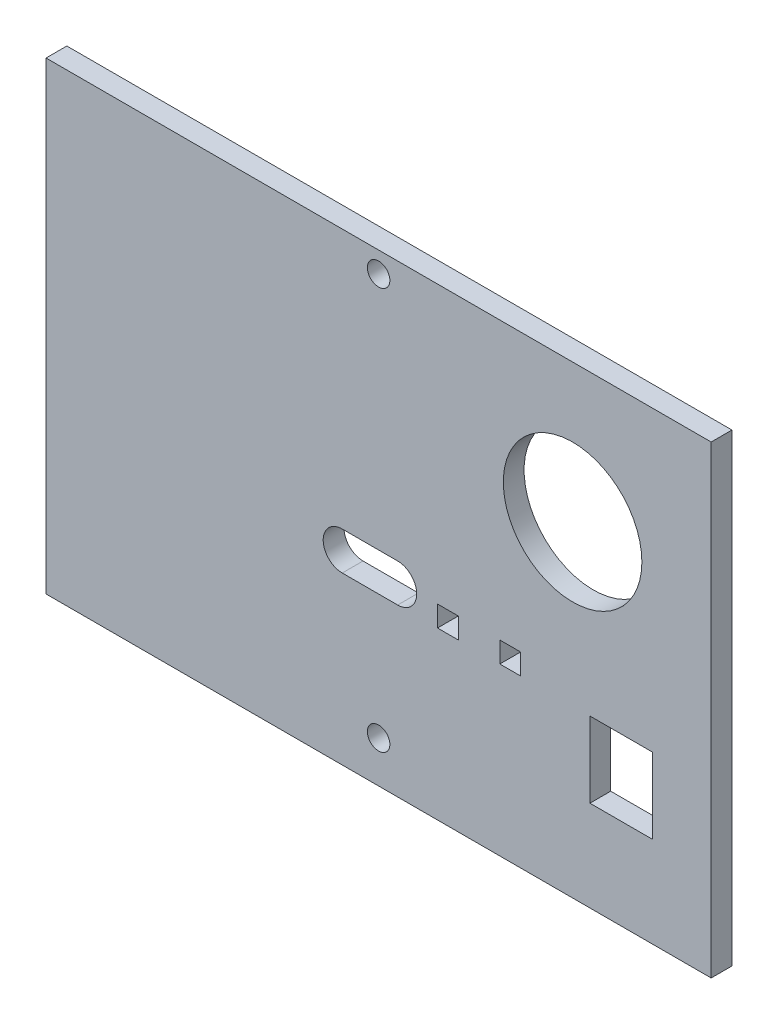
SolidWorks part; units mm, degrees
ref_plane "Alzado" through (0, 0, 0) normal (0, 0, 1) x (1, 0, 0)
ref_plane "Planta" through (0, 0, 0) normal (0, 1, 0) x (1, 0, 0)
ref_plane "Vista lateral" through (0, 0, 0) normal (1, 0, 0) x (0, 0, -1)
sketch "Croquis6" plane through (0, 0, 0) normal (0, 0, 1) x (1, 0, 0)
  line L1 (-48, -33.5) -> (48, -33.5)
  line L2 (-48, -33.5) -> (-48, 33.5)
  line L3 (-48, 33.5) -> (48, 33.5)
  line L4 (48, -33.5) -> (48, 33.5)
  line L5 (-48, -33.5) -> (48, 33.5) construction
  line L6 (-48, 33.5) -> (48, -33.5) construction
  point P0 (0, 0)
  dimension "D1" = 96
  dimension "D2" = 67
extrude "Saliente-Extruir1" add sketch "Croquis6" along normal blind 3
sketch "Croquis7" plane through (0, 0, 0) normal (0, 0, 1) x (1, 0, 0)
  line L5 (48, 33.5) -> (-48, 33.5) construction
  line L13 (-48, -33.5) -> (48, -33.5) construction
  line L14 (30.5, -9.5) -> (39.5, -9.5)
  line L15 (30.5, -9.5) -> (30.5, -20.4)
  line L16 (30.5, -20.4) -> (39.5, -20.4)
  line L17 (39.5, -9.5) -> (39.5, -20.4)
  line L18 (30.5, -9.5) -> (39.5, -20.4) construction
  line L19 (30.5, -20.4) -> (39.5, -9.5) construction
  line L20 (-48, 33.5) -> (-48, -33.5) construction
  line L21 (2.75, -6.75) -> (-5.25, -6.75) construction
  line L22 (2.75, -9.5) -> (-5.25, -9.5)
  line L23 (2.75, -4) -> (-5.25, -4)
  line L24 (48, -33.5) -> (48, 33.5) construction
  line L25 (8.5, -9.5) -> (11.5, -9.5)
  line L26 (8.5, -9.5) -> (8.5, -6.5)
  line L27 (8.5, -6.5) -> (11.5, -6.5)
  line L28 (11.5, -9.5) -> (11.5, -6.5)
  line L29 (8.5, -9.5) -> (11.5, -6.5) construction
  line L30 (8.5, -6.5) -> (11.5, -9.5) construction
  line L32 (17.5, -9.5) -> (20.5, -9.5)
  line L33 (17.5, -9.5) -> (17.5, -6.5)
  line L34 (17.5, -6.5) -> (20.5, -6.5)
  line L35 (20.5, -9.5) -> (20.5, -6.5)
  line L36 (17.5, -9.5) -> (20.5, -6.5) construction
  line L37 (17.5, -6.5) -> (20.5, -9.5) construction
  arc A0 (2.75, -9.5) -> (2.75, -4) centre (2.75, -6.75) ccw
  arc A1 (-5.25, -4) -> (-5.25, -9.5) centre (-5.25, -6.75) ccw
  circle A2 centre (0, -27.5) radius 1.625 construction
  circle A3 centre (0, 30.5) radius 1.625 construction
  circle A4 centre (0, -27.5) radius 1.625
  circle A5 centre (0, 30.5) radius 1.625
  circle A6 centre (28, 13.5) radius 10
  point P2 (0, 0)
  point P3 (35, 21.3965)
  point P4 (35, 19.4387)
  point P5 (19, 15.7094)
  point P12 (35, -14.95)
  point P23 (-1.25, -6.75)
  point P34 (10, -8)
  point P41 (19, -8)
  dimension "D11" = 42.75
  dimension "D12" = 39.5
  dimension "D2" = 20
  dimension "D3" = 20
  dimension "D4" = 20
  dimension "D5" = 10.9
  dimension "D6" = 9
  dimension "D7" = 24
  dimension "D8" = 87.5
  dimension "D9" = 8
  dimension "D10" = 5.5
  dimension ".5" = 29.5
  dimension "D13" = 24
  dimension "D14" = 3
  dimension "D15" = 6
extrude "Cortar-Extruir1" cut sketch "Croquis7" along normal through all
sketch "Sketch3" plane through (0, 0, 0) normal (0, 0, -1) x (-1, 0, 0)
  line L0 (0.3471, -0.1213) -> (0.4863, 0.0193)
  line L1 (0.4863, 0.0193) -> (-0.8214, 1.3302)
  line L2 (-2.1938, 4.0023) -> (-2.1938, 5.2355)
  line L3 (-2.1938, 5.2355) -> (-2.305, 5.3057)
  line L4 (-1.1344, 5.3242) -> (-1.2539, 5.2509)
  line L5 (-1.2539, 5.2509) -> (-1.2538, 4.1659)
  line L6 (-1.2538, 4.1659) -> (-1.2537, 3.0809)
  line L7 (-1.2537, 3.0809) -> (-0.2805, 2.0692)
  line L8 (0.7386, 5.1898) -> (0.7386, 9.3416)
  line L9 (0.7386, 9.3416) -> (0.366, 9.6084)
  line L10 (2.1031, 9.6083) -> (1.6769, 9.3415)
  line L11 (1.6769, 9.3415) -> (1.6769, 6.2748)
  line L12 (1.6769, 6.2748) -> (1.6769, 3.2081)
  line L13 (1.6769, 3.2081) -> (2.7326, 4.2436)
  line L14 (2.7326, 4.2436) -> (3.7882, 5.2791)
  line L15 (3.7882, 5.2791) -> (3.7882, 6.0201)
  line L16 (3.7882, 6.0201) -> (3.7882, 6.761)
  line L17 (3.7882, 6.761) -> (3.5517, 6.761)
  line L18 (3.2018, 7.7887) -> (3.2018, 8.7558)
  line L19 (3.2018, 8.7558) -> (4.2501, 8.7478)
  line L20 (4.2501, 8.7478) -> (5.2984, 8.7398)
  line L21 (5.2984, 8.7398) -> (5.3064, 7.7789)
  line L22 (5.3064, 7.7789) -> (5.3144, 6.8179)
  line L23 (5.3144, 6.8179) -> (5.2388, 6.7892)
  line L24 (4.9452, 6.7605) -> (4.7272, 6.7605)
  line L25 (4.7272, 6.7605) -> (4.7272, 5.9092)
  line L26 (3.1572, 3.3794) -> (1.6775, 1.9169)
  line L27 (1.6775, 1.9169) -> (1.6775, 1.0456)
  line L28 (1.6775, 1.0456) -> (1.6775, 0.1743)
  line L29 (1.6775, 0.1743) -> (1.8112, 0.1093)
  line L30 (1.0062, -2.2401) -> (1.0057, -2.239)
  spline S0 degree 3 poles (1.0057, -2.239) (0.7865, -2.196) (0.5245, -2.0539) (0.3588, -1.8881) knots 0 0 0 0 1 1 1 1
  spline S1 degree 3 poles (0.3588, -1.8881) (-0.1277, -1.4016) (-0.133, -0.6065) (0.3471, -0.1213) knots 0 0 0 0 1 1 1 1
  spline S2 degree 3 poles (-0.8214, 1.3302) (-1.5406, 2.0512) (-2.1436, 2.6699) (-2.1614, 2.7051) knots 0 0 0 0 1 1 1 1
  spline S3 degree 3 poles (-2.1614, 2.7051) (-2.1835, 2.7488) (-2.1938, 3.1607) (-2.1938, 4.0023) knots 0 0 0 0 1 1 1 1
  spline S4 degree 3 poles (-2.305, 5.3057) (-2.5818, 5.4804) (-2.762, 5.8041) (-2.7641, 6.1306) knots 0 0 0 0 1 1 1 1
  spline S5 degree 3 poles (-2.7641, 6.1306) (-2.7661, 6.3924) (-2.7166, 6.5594) (-2.5789, 6.7593) knots 0 0 0 0 1 1 1 1
  spline S6 degree 3 poles (-2.5789, 6.7593) (-2.151, 7.3807) (-1.216, 7.332) (-0.8365, 6.6686) knots 0 0 0 0 1 1 1 1
  spline S7 degree 3 poles (-0.8365, 6.6686) (-0.5765, 6.2142) (-0.717, 5.5802) (-1.1344, 5.3242) knots 0 0 0 0 1 1 1 1
  spline S8 degree 3 poles (-0.2805, 2.0692) (0.2548, 1.5128) (0.7031, 1.0532) (0.7157, 1.0478) knots 0 0 0 0 1 1 1 1
  spline S9 degree 3 poles (0.7157, 1.0478) (0.7283, 1.0428) (0.7386, 2.9063) (0.7386, 5.1898) knots 0 0 0 0 1 1 1 1
  spline S10 degree 3 poles (0.366, 9.6084) (-0.0422, 9.6084) (-0.1161, 9.6313) (-0.1161, 9.7578) knots 0 0 0 0 1 1 1 1
  spline S11 degree 3 poles (-0.1161, 9.7578) (-0.1161, 9.7971) (0.1643, 10.522) (0.5069, 11.3684) knots 0 0 0 0 1 1 1 1
  spline S12 degree 3 poles (0.5069, 11.3684) (0.8496, 12.2148) (1.1361, 12.9233) (1.1438, 12.9428) knots 0 0 0 0 1 1 1 1
  spline S13 degree 3 poles (1.1438, 12.9428) (1.1658, 12.9995) (1.2718, 13.0203) (1.3144, 12.9762) knots 0 0 0 0 1 1 1 1
  spline S14 degree 3 poles (1.3144, 12.9762) (1.3631, 12.9259) (2.6184, 9.8224) (2.6184, 9.7524) knots 0 0 0 0 1 1 1 1
  spline S15 degree 3 poles (2.6184, 9.7524) (2.6184, 9.6277) (2.5491, 9.6083) (2.1031, 9.6083) knots 0 0 0 0 1 1 1 1
  spline S16 degree 3 poles (3.5517, 6.761) (3.1693, 6.761) (3.2018, 6.6657) (3.2018, 7.7887) knots 0 0 0 0 1 1 1 1
  spline S17 degree 3 poles (5.2388, 6.7892) (5.1972, 6.7734) (5.0651, 6.7605) (4.9452, 6.7605) knots 0 0 0 0 1 1 1 1
  spline S18 degree 3 poles (4.7272, 5.9092) (4.7272, 5.2092) (4.7192, 5.0386) (4.6821, 4.9499) knots 0 0 0 0 1 1 1 1
  spline S19 degree 3 poles (4.6821, 4.9499) (4.6511, 4.8755) (4.1757, 4.386) (3.1572, 3.3794) knots 0 0 0 0 1 1 1 1
  spline S20 degree 3 poles (1.8112, 0.1093) (2.0985, -0.0302) (2.3701, -0.3691) (2.4573, -0.6967) knots 0 0 0 0 1 1 1 1
  spline S21 degree 3 poles (2.4573, -0.6967) (2.641, -1.3866) (2.1812, -2.1075) (1.4716, -2.2421) knots 0 0 0 0 1 1 1 1
  spline S22 degree 3 poles (1.4716, -2.2421) (1.2944, -2.2757) (1.1872, -2.2751) (1.0062, -2.2401) knots 0 0 0 0 1 1 1 1
